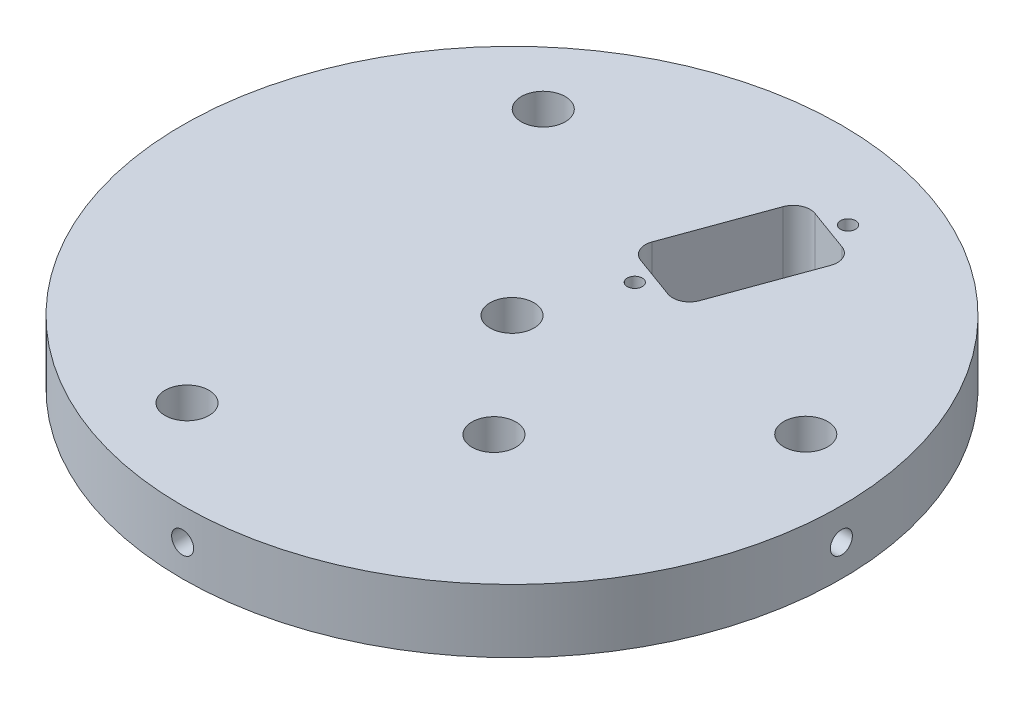
SolidWorks part; units mm, degrees
material "6061-T6 (SS)"
ref_plane "Front Plane" through (0, 0, 0) normal (0, 0, 1) x (1, 0, 0)
ref_plane "Top Plane" through (0, 0, 0) normal (0, 1, 0) x (1, 0, 0)
ref_plane "Right Plane" through (0, 0, 0) normal (1, 0, 0) x (0, 0, -1)
sketch "Sketch1" plane through (0, 0, 0) normal (0, 1, 0) x (1, 0, 0)
  line L0 (0, 0) -> (-50.3682, 60.0265)
  line L1 (0, 0) -> (50.3682, 60.0265)
  line L2 (0, 0) -> (0, 72.1431) construction
  circle A0 centre (0, 0) radius 78.359
  circle A1 centre (0, 0) radius 51.1048
  circle A2 centre (0, 0) radius 76.1746
  dimension "D1" = 156.718
  dimension "D2" = 102.2096
  dimension "D3" = 152.3492
  dimension "D4" = 80
extrude "Boss-Extrude1" add sketch "Sketch1" along normal blind 25.4 contours L2 A2 L1 A0 | L2 A1 L1 A2 | L2 A2 L1 A1 | L2 A0 L1 A2 | A2 L2 A1 L0 | A0 L2 A2 L0 | A2 L2 A0 L0 | A1 L2 A2 L0 region at (-22.4568, 0, 48.1587) region at (-40.1048, 0, -49.4238) region at (-33.0764, 0, 70.9325) region at (-48.8794, 0, -59.85)
ref_plane "Plane1" through (0, 12.7, 0) normal (0, 1, 0) x (1, 0, 0)
sketch "Sketch6" plane through (0, 25.4, 0) normal (0, 1, 0) x (1, 0, 0)
  circle A0 centre (0, 0) radius 49.5173
  dimension "D1" = 99.0346
extrude "Boss-Extrude5" add sketch "Sketch6" along normal blind 9.525
sketch "Sketch7" plane through (0, 0, 0) normal (0, -1, 0) x (1, 0, 0)
  circle A0 centre (0, 0) radius 49.5173
  dimension "D1" = 99.0346
extrude "Boss-Extrude6" add sketch "Sketch7" along normal blind 9.525
sketch "Sketch8" plane through (0, -9.525, 0) normal (0, -1, 0) x (1, 0, 0)
  circle A0 centre (0, 0) radius 46.99
  dimension "D1" = 93.98
ref_plane "Plane2" through (0, 0, -49.5173) normal (0, 0, -1) x (-1, 0, 0)
ref_plane "Plane5" through (0, 25.4, 0) normal (0, 1, 0) x (1, 0, 0)
ref_axis "Axis1" through (0, 0, 0) along (0, 1, 0)
ref_plane "Plane3" through (0, 34.925, 0) normal (0, 1, 0) x (1, 0, 0)
sketch "Sketch9" plane through (0, 34.925, 0) normal (0, 1, 0) x (1, 0, 0)
  line L0 (0, 0) -> (-26.8004, -73.6334) construction
  line L1 (0, 0) -> (32.0596, -38.2071) construction
  line L2 (0, 0) -> (0, -86.0416) construction
  circle A0 centre (0, 0) radius 3.3
  circle A1 centre (-13.031, -35.8023) radius 3.3
  circle A4 centre (14.1499, -16.8632) radius 3.3
  circle A5 centre (-24.4902, 29.1863) radius 3.3
  circle A6 centre (37.5212, 6.616) radius 3.3
  point P15 (-1.3039, -1.0954)
  point P18 (0, 0)
  dimension "D1" = 6.6
  dimension "D2" = 6.6
  dimension "D6" = 6.6
  dimension "D3" = 38.1
  dimension "D4" = 60
  dimension "D7" = 22.0133
  dimension "D8" = 20
extrude "Cut-Extrude6" cut sketch "Sketch9" against normal through all
sketch "Sketch10" plane through (0, 25.4, 0) normal (0, 1, 0) x (1, 0, 0)
  circle A0 centre (0, 0) radius 82.3228
extrude "Cut-Extrude7" cut sketch "Sketch10" against normal through all
hole_wizard "Tap Drill for #4-40 Tap1" positions "Sketch12" profile "Sketch13" hole size "#4-40" standard "ANSI Inch" end condition through all
sketch "Sketch12" plane through (0, 34.925, 0) normal (0, 1, 0) x (1, 0, 0)
  line L0 (0, 0) -> (18.6243, 51.1699) construction
  line L2 (0, 0) -> (-24.4902, 29.1863) construction
  circle A0 centre (0, 0) radius 14.3933 construction
  point P0 (4.9228, 13.5253)
  point P2 (13.4733, 37.0176)
  dimension "D3" = 28.7867
  dimension "D1" = 60
  dimension "D2" = 25
sketch "Sketch13" plane through (4.9228, 34.925, -13.5253) normal (1, 0, 0) x (0, 0, 1)
  line L0 (0, 0) -> (0, 9.525)
  line L1 (0, 9.525) -> (1.1303, 9.525)
  line L2 (1.1303, 9.525) -> (1.1303, 0)
  line L5 (1.1303, 0) -> (0, 0)
  line L11 (0, -6.35) -> (0, 107.95) construction
  dimension "Thru Hole Dia." = 2.2606
  dimension "Thru Hole Depth" = 9.525
sketch "Sketch14" plane through (0, 34.925, 0) normal (0, 1, 0) x (1, 0, 0)
  line L0 (4.9228, 13.5253) -> (13.4733, 37.0176) construction
  line L1 (12.1824, 16.0187) -> (17.4317, 30.4411)
  line L2 (8.9269, 14.5007) -> (2.4825, 16.8462)
  line L3 (15.9137, 33.6967) -> (9.4692, 36.0423)
  line L4 (0.9644, 20.1018) -> (6.2137, 34.5242)
  arc A0 (17.4317, 30.4411) -> (15.9137, 33.6967) centre (15.0449, 31.3099) ccw
  arc A1 (9.4692, 36.0423) -> (6.2137, 34.5242) centre (8.6005, 33.6555) ccw
  arc A2 (8.9269, 14.5007) -> (12.1824, 16.0187) centre (9.7956, 16.8875) ccw
  arc A3 (2.4825, 16.8462) -> (0.9644, 20.1018) centre (3.3512, 19.2331) cw
  point P0 (5.7047, 15.6734)
  dimension "D4" = 2.54
  dimension "D5" = 2.54
  dimension "D2" = 2.286
  dimension "D3" = 11.938
extrude "Cut-Extrude9" cut sketch "Sketch14" against normal through all
ref_plane "Plane6" through (49.5173, 0, 0) normal (1, 0, 0) x (0, 0, -1)
hole_wizard "Tap Drill for M4x0.7 Tap1" positions "Sketch16" profile "Sketch17" hole size "M4x0.7" standard "ANSI Metric"
sketch "Sketch16" plane through (49.5173, 0, 0) normal (1, 0, 0) x (0, 0, -1)
  line L1 (49.5173, 34.925) -> (-49.5173, 34.925) construction
  point P0 (0, 30.1625)
  dimension "D1" = 4.7625
sketch "Sketch17" plane through (49.5173, 30.1625, 0) normal (0, 1, 0) x (0, 0, -1)
  line L0 (0, 0) -> (0, 10.6434)
  line L1 (0, 10.6434) -> (1.65, 9.652)
  line L2 (1.65, 9.652) -> (1.65, 0)
  line L5 (1.65, 0) -> (0, 0)
  line L10 (0, 10.6434) -> (-1.65, 9.652) construction
  line L11 (0, -6.35) -> (0, 107.95) construction
  dimension "Hole Dia." = 3.3
  dimension "Hole Depth" = 9.652
  dimension "Drill Angle" = 118
pattern_circular "CirPattern1" count 4 over 360 about axis through (0, 34.925, 0) along (0, 1, 0) of "Tap Drill for M4x0.7 Tap1"
equation "\"AB_Coupler_OD_Length\"= 1in"
equation "\"AB_Coupling_Section_Length\"= 0.375in"
equation "\"AB_Coupler_Length\"= \"AB_Coupler_OD_Length\" + \"AB_Coupling_Section_Length\" * 2"
equation "\"Cutout_Angle\" = 60"
equation "\"AB_Coupler_Num_Screws\"= 4"
equation "\"Num_Cutouts\" = 4"
equation "\"AB_Coupler_OD\"= 4.024in"
equation "\"AB_Coupler_ID\"= 3.7in"
equation "\"AB_Coupler_Surface_Diameter\"= 3.899in"
equation "\"D2@Sketch1\"= \"Body_Tube_OD\""
equation "\"AB_Coupling_Screw_Diameter\"= 0.1065in"
equation "\"Aft_Section_Length\" = 32in"
equation "\"Mid_Coupler_Length\" = 12in"
equation "\"Lead_Screw_Dist\" = 2in"
equation "\"Lead_Screw_Diam\" = 0.375in"
equation "\"Lead_Screw_Length\" = \"Mid_Coupler_Length\" + 2*0.375in + 2*0.5in"
equation "\"Paddle_Pin_Offset\" = 0.25in"
equation "\"Paddle_Pin_Radius\" = 2.25*2/3in"
equation "\"D1@Sketch6\"=\"AB_Coupler_Surface_Diameter\""
equation "\"D1@Boss-Extrude5\"=\"AB_Coupling_Section_Length\""
equation "\"D1@Sketch7\"=\"AB_Coupler_Surface_Diameter\""
equation "\"D1@Boss-Extrude6\"=\"AB_Coupling_Section_Length\""
equation "\"D1@Sketch8\"=\"AB_Coupler_ID\""
equation "\"D3@Sketch9\"=\"Paddle_Pin_Radius\""
equation "\"Motor_OD\" = 54mm"
equation "\"AB_Paddle_Height\" = 0.375in"
equation "\"AB_Central_Bushing_Length\" = 0.75in"
equation "\"Paddle_Gear_OD\" = 3.2in"
equation "\"Fwd_BKHD_From_Top\" = 18in"
equation "\"Fin_Thickness\" = 0.118in"
equation "\"DB9_Hole_Dist\" = 25mm"
equation "\"D2@Sketch12\"=\"DB9_Hole_Dist\""
equation "\"Drive_Gear_OD\" = 1.7*2/3in"
equation "\"D3@Sketch12\"=\"Drive_Gear_OD\""
equation "\"DB9_Relief_Width\" = 0.47in"
equation "\"D3@Sketch14\"=\"DB9_Relief_Width\""
equation "\"DB9_Relief_Hole_Offset\" = 0.09in"
equation "\"D2@Sketch14\"=\"DB9_Relief_Hole_Offset\""
equation "\"D1@Sketch14\"=\"DB9_Relief_Hole_Offset\""
equation "\"Airbrakes_Wire_Hole_Dia\" = 0.25in"
equation "\"Airbrakes_Wire_Hole_Dist\" = 1.1in"
equation "\"Servo_Gear_Offset\" = 0.5in"
equation "\"Motor_Length\" = 401mm"
equation "\"Body_Tube_OD\"= 4.024in"
equation "\"Body_Tube_ID\"= 3.90in"
equation "\"Coupler_OD\" = 3.899in"
equation "\"Coupler_ID\" = 3.755in"
equation "\"Fwd_Section_Length\" = 20in"
equation "\"Mid_Section_Length\" = 4in"
equation "\"Aft_Upper_Tube_Length\" = 10in"
equation "\"Aft_Lower_Tube_Length\" = 18in"
equation "\"Nosecone_Coupler_Length\" = 5in"
equation "\"Avionics_Bulkhead_Thickness\" = 0.25in"
equation "\"Avionics_Bulkhead_Lip\" = 0.125in"
equation "\"Avionics_Board_Length\" = \"Mid_Coupler_Length\" - 2*\"Avionics_Bulkhead_Lip\""
equation "\"Lead_Screw_Hole_Diam\" = 0.386in"
equation "\"Centering_Ring_Cutout_Dia\"=1.5in"
equation "\"D7@Sketch9\"=\"Drive_Gear_OD\"/2+.3"
equation "\"D1@Sketch16\"=.375/2"
